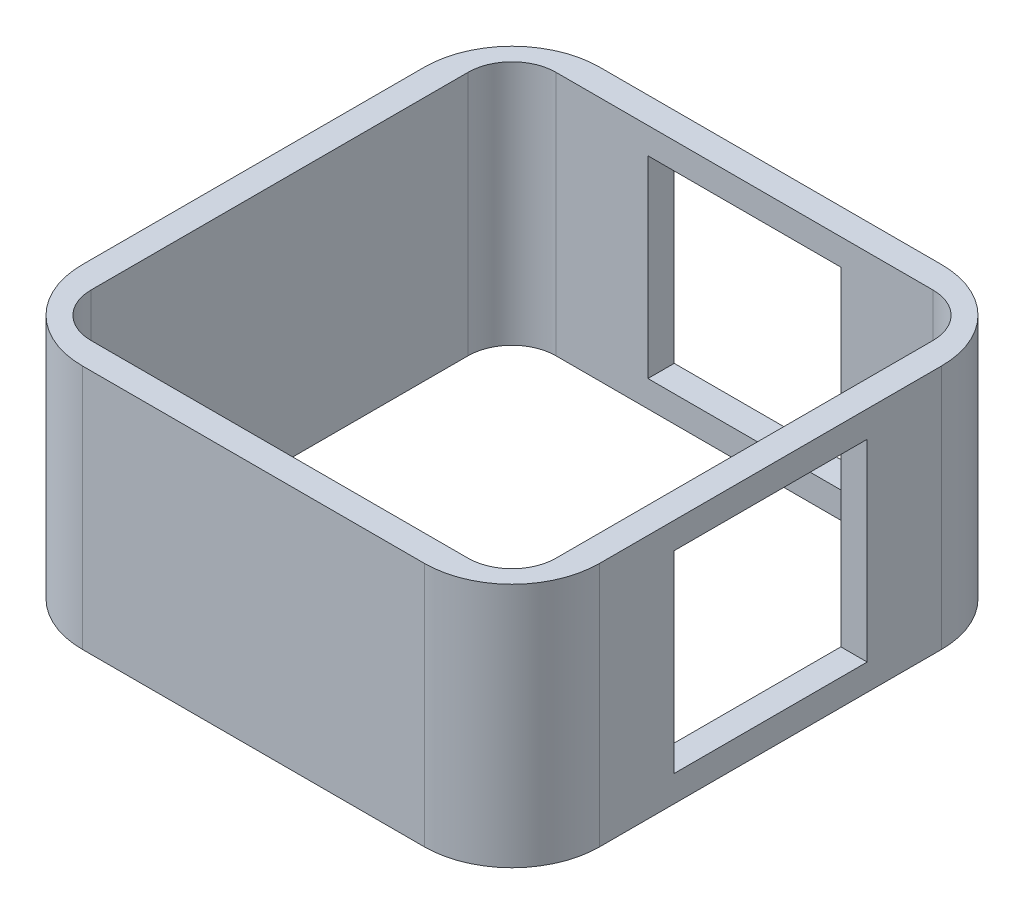
SolidWorks part; units mm, degrees
ref_plane "Front Plane" through (0, 0, 0) normal (0, 0, 1) x (1, 0, 0)
ref_plane "Top Plane" through (0, 0, 0) normal (0, 1, 0) x (1, 0, 0)
ref_plane "Right Plane" through (0, 0, 0) normal (1, 0, 0) x (0, 0, -1)
sketch "Sketch1" plane through (0, 0, 0) normal (0, 1, 0) x (1, 0, 0)
  line L1 (-29.5, -29.5) -> (29.5, -29.5)
  line L2 (-29.5, -29.5) -> (-29.5, 29.5)
  line L3 (-29.5, 29.5) -> (29.5, 29.5)
  line L4 (29.5, -29.5) -> (29.5, 29.5)
  line L5 (-29.5, -29.5) -> (29.5, 29.5) construction
  line L6 (-29.5, 29.5) -> (29.5, -29.5) construction
  line L7 (-26.5, -26.5) -> (26.5, -26.5)
  line L8 (-26.5, -26.5) -> (-26.5, 26.5)
  line L9 (-26.5, 26.5) -> (26.5, 26.5)
  line L10 (26.5, -26.5) -> (26.5, 26.5)
  line L11 (-26.5, -26.5) -> (26.5, 26.5) construction
  line L12 (-26.5, 26.5) -> (26.5, -26.5) construction
  point P0 (0, 0)
  point P6 (0, 0)
  dimension "D1" = 3
  dimension "D2" = 3
  dimension "D3" = 53
  dimension "D4" = 53
extrude "Boss-Extrude1" add sketch "Sketch1" along normal blind 28
fillet "Fillet1" radius 10 4 edges at (29.5, 14, -29.5) (29.5, 14, 29.5) (-29.5, 14, 29.5) (-29.5, 14, -29.5)
fillet "Fillet2" radius 5 4 edges at (-26.5, 14, -26.5) (-26.5, 14, 26.5) (26.5, 14, 26.5) (26.5, 14, -26.5)
sketch "Sketch3" plane through (0, 0, -29.5) normal (0, 0, -1) x (-1, 0, 0)
  line L23 (0, 16.5) -> (0, -16.5) construction
  line L24 (-11, 3) -> (11, 3)
  line L25 (-11, 3) -> (-11, 25)
  line L26 (-11, 25) -> (11, 25)
  line L27 (11, 3) -> (11, 25)
  line L28 (-11, 3) -> (11, 25) construction
  line L29 (-11, 25) -> (11, 3) construction
  line L30 (32.45, 0) -> (-32.45, 0) construction
  point P0 (0, 14)
  dimension "D1" = 22
  dimension "D2" = 22
  dimension "D3" = 14
extrude "Cut-Extrude2" cut sketch "Sketch3" against normal blind 3
sketch "Sketch5" plane through (29.5, 0, 0) normal (1, 0, 0) x (0, 0, -1)
  line L0 (0, 15.4) -> (0, -15.4) construction
  line L1 (-11, 3) -> (11, 3)
  line L2 (-11, 3) -> (-11, 25)
  line L3 (-11, 25) -> (11, 25)
  line L4 (11, 3) -> (11, 25)
  line L5 (-11, 3) -> (11, 25) construction
  line L6 (-11, 25) -> (11, 3) construction
  line L7 (-19.5, 28) -> (19.5, 28) construction
  point P0 (0, 14)
  dimension "D1" = 3
  dimension "D2" = 22
  dimension "D3" = 22
extrude "Cut-Extrude4" cut sketch "Sketch5" against normal up to next
